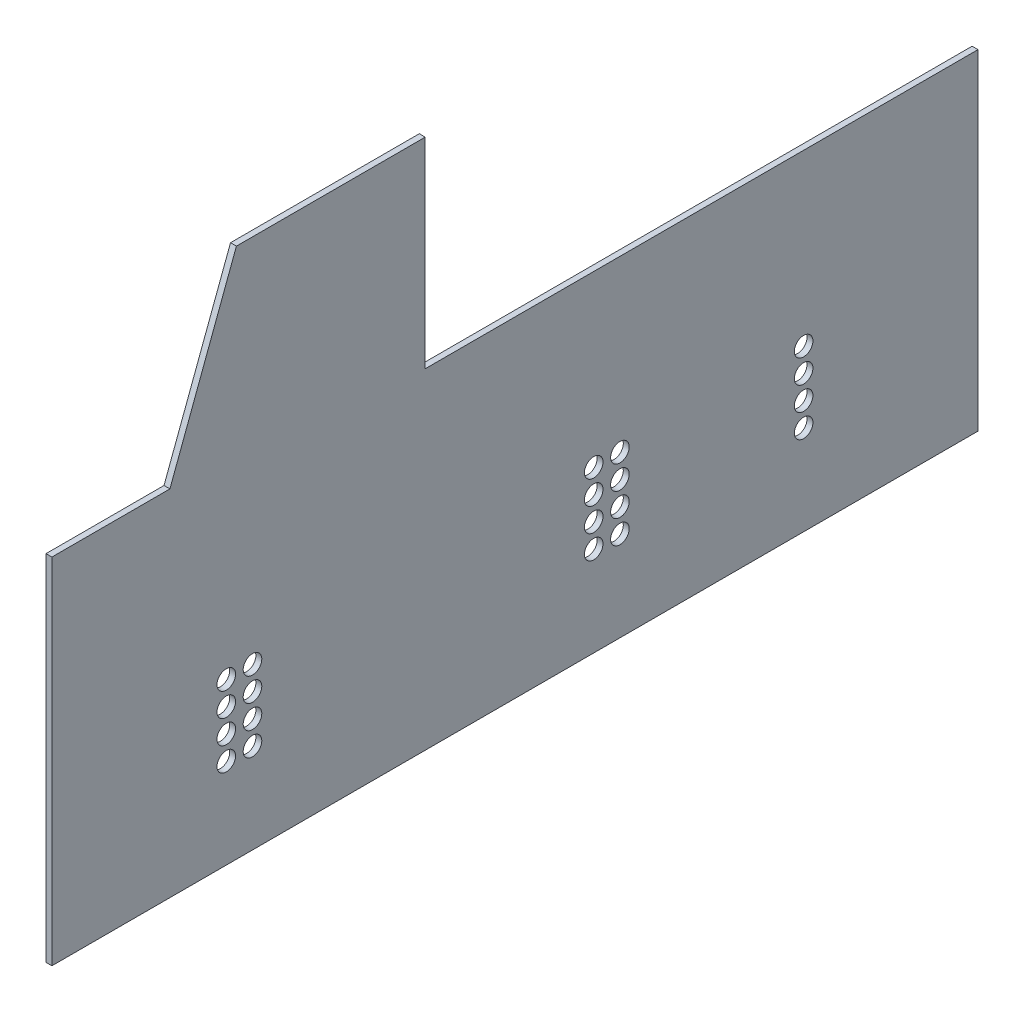
SolidWorks part; units mm, degrees
material "6061-T6 (SS)"
ref_plane "X-Y Datum" through (0, 0, 0) normal (0, 0, 1) x (1, 0, 0)
ref_plane "X-Z Datum" through (0, 0, 0) normal (0, 1, 0) x (1, 0, 0)
ref_plane "Y-Z Datum" through (0, 0, 0) normal (1, 0, 0) x (0, 0, -1)
sketch "Sketch1" plane through (0, 0, 0) normal (1, 0, 0) x (0, 0, -1)
  line L1 (-249.174, 88.9) -> (249.174, 88.9)
  line L2 (-249.174, 88.9) -> (-249.174, -88.9)
  line L3 (-249.174, -88.9) -> (249.174, -88.9)
  line L4 (249.174, 88.9) -> (249.174, -88.9)
  line L5 (-249.174, 88.9) -> (249.174, -88.9) construction
  line L6 (-249.174, -88.9) -> (249.174, 88.9) construction
  point P0 (0, 0)
  dimension "D1" = 177.8
  dimension "D2" = 498.348
extrude "Boss-Extrude1" add sketch "Sketch1" along normal mid plane 3.175
sketch "Sketch2" plane through (-1.5875, 0, 0) normal (-1, 0, 0) x (0, 0, 1)
  line L0 (48.2854, 88.9) -> (249.174, 88.9)
  line L1 (-249.174, 88.9) -> (249.174, 88.9) construction
  line L2 (249.174, 88.9) -> (249.174, 101.6)
  line L4 (48.2854, -85.725) -> (48.2854, 219.075)
  line L17 (249.174, 101.6) -> (185.674, 101.6)
  line L18 (185.674, 101.6) -> (149.8854, 196.85)
  line L19 (149.8854, 196.85) -> (48.2854, 196.85)
  line L20 (48.2854, 196.85) -> (48.2854, 88.9)
  line M14 (249.174, 88.9) -> (-249.174, 88.9)
  dimension "D1" = 12.7
  dimension "D2" = 63.5
  dimension "D3" = 107.95
  dimension "D4" = 101.6
extrude "Boss-Extrude2" add sketch "Sketch2" against normal blind 3.175 contours L18 L19 L4 L2 L17 M14 region at (-1.5875, 137.3997, 115.8494)
sketch "Sketch3" plane through (-1.5875, 0, 0) normal (-1, 0, 0) x (0, 0, 1)
  circle A38 centre (141.2367, -27.7749) radius 5
  circle A40 centre (155.3337, -27.7749) radius 5
extrude "Cut-Extrude3" cut sketch "Sketch3" against normal through all contours A40 region at (-1.5875, -27.7749, 155.3337)
pattern_linear "LPattern3" count 3 spacing 12.7 along (0, 1, 0) count 2 spacing 12.7 along (0, -1, 0) of "Cut-Extrude3"
pattern_linear "LPattern4" count 2 spacing 197.7136 along (0, 0, -1) of "LPattern3"
sketch "Sketch5" plane through (-1.5875, 0, 0) normal (-1, 0, 0) x (0, 0, 1)
  circle A1 centre (155.3337, -27.7749) radius 5
  circle A2 centre (155.3337, -27.7749) radius 5
  circle A3 centre (141.2367, -27.7749) radius 5
  circle A4 centre (141.2367, -27.7749) radius 5
  dimension "D1" = 0
  dimension "D2" = 0
extrude "Cut-Extrude4" cut sketch "Sketch5" against normal through all contours A4 region at (-1.5875, -27.7749, 141.2367)
pattern_linear "LPattern5" count 3 spacing 12.7 along (0, 1, 0) count 2 spacing 12.7 along (0, -1, 0) of "Cut-Extrude4"
pattern_linear "LPattern6" count 4 spacing 98.8568 along (0, 0, -1) skipping (1, 0) of "LPattern5"
